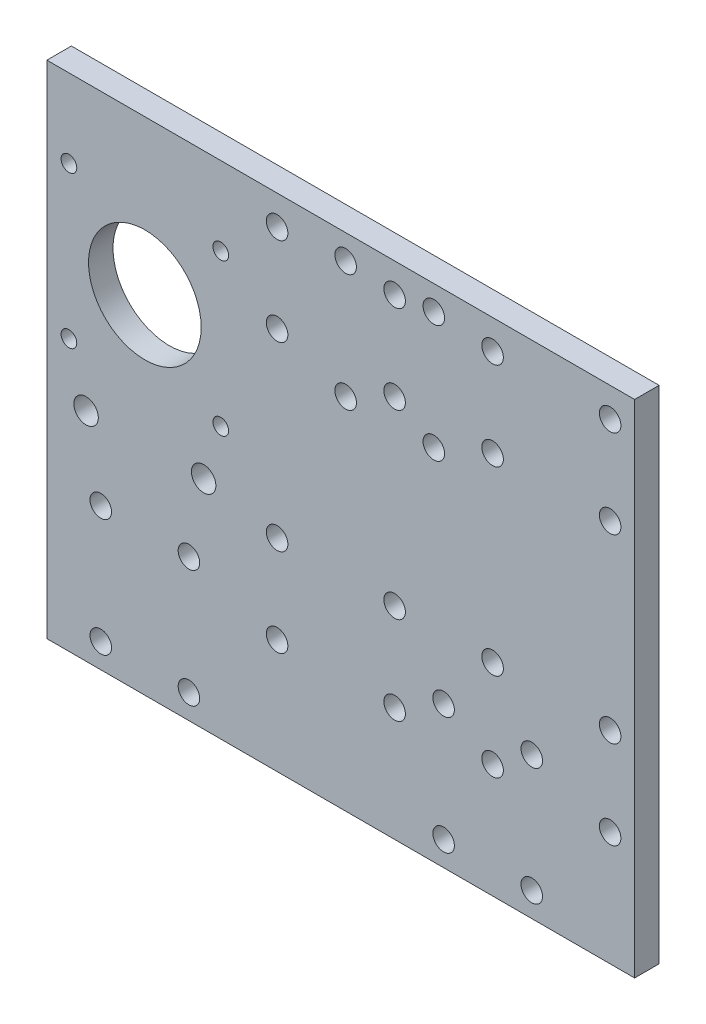
SolidWorks part; units mm, degrees
ref_plane "Front Plane" through (0, 0, 0) normal (0, 0, 1) x (1, 0, 0)
ref_plane "Top Plane" through (0, 0, 0) normal (0, 1, 0) x (1, 0, 0)
ref_plane "Right Plane" through (0, 0, 0) normal (1, 0, 0) x (0, 0, -1)
sketch "Sketch1" plane through (0, 0, 0) normal (0, 0, 1) x (1, 0, 0)
  line L1 (-60, 51.15) -> (60, 51.15)
  line L2 (-60, 51.15) -> (-60, -51.15)
  line L3 (-60, -51.15) -> (60, -51.15)
  line L4 (60, 51.15) -> (60, -51.15)
  line L5 (-60, 51.15) -> (60, -51.15) construction
  line L6 (-60, -51.15) -> (60, 51.15) construction
  point P0 (0, 0)
  dimension "D1" = 102.3
  dimension "D2" = 120
extrude "Boss-Extrude1" add sketch "Sketch1" along normal blind 5
sketch "Sketch4" plane through (0, 0, 5) normal (0, 0, 1) x (1, 0, 0)
  line L0 (21, -22.15) -> (39, -22.15) construction
  line L1 (39, -22.15) -> (39, -46.15) construction
  line L2 (39, -46.15) -> (21, -46.15) construction
  line L3 (21, -46.15) -> (21, -22.15) construction
  circle A0 centre (39, -22.15) radius 2.2
  circle A1 centre (39, -46.15) radius 2.2
  circle A2 centre (21, -46.15) radius 2.2
  circle A3 centre (21, -22.15) radius 2.2
  dimension "D7" = 4.4
  dimension "D1" = 24
  dimension "D2" = 18
extrude "Cut-Extrude1" cut sketch "Sketch4" against normal blind 5
pattern_linear "LPattern1" count 2 spacing 70 along (-1, 0, 0) of "Cut-Extrude1"
sketch "Sketch6" plane through (0, 0, 5) normal (0, 0, 1) x (1, 0, 0)
  line L0 (-55.5, 35.1494) -> (-24.5, 35.1506) construction
  line L5 (-24.5, 35.1506) -> (-24.5, 4.1506) construction
  line L6 (60, 51.15) -> (-60, 51.15) construction
  line L11 (-55.5, 35.1494) -> (-24.5, 4.1506) construction
  line L12 (-55.5, 4.1494) -> (-24.5, 35.1506) construction
  line L13 (-60, 51.15) -> (-60, -51.15) construction
  line L14 (-24.5, 4.1506) -> (-55.5, 4.1494) construction
  line L15 (-55.5, 4.1494) -> (-55.5, 35.1494) construction
  circle A0 centre (-55.5, 35.1494) radius 1.6
  circle A1 centre (-24.5, 35.1506) radius 1.6
  circle A2 centre (-55.5, 4.1494) radius 1.6
  circle A3 centre (-24.5, 4.1506) radius 1.6
  circle A4 centre (-40, 19.65) radius 11.5
  point P9 (-40, 19.65)
  dimension "D1" = 31.5
  dimension "D2" = 20
  dimension "D3" = 31
  dimension "D4" = 31
extrude "Cut-Extrude4" cut sketch "Sketch6" against normal blind 10
sketch "Sketch8" plane through (0, 0, 5) normal (0, 0, 1) x (1, 0, 0)
  line L0 (11, 27.15) -> (-13, 45.15) construction
  line L5 (-13, 27.15) -> (11, 45.15) construction
  line L6 (60, 51.15) -> (-60, 51.15) construction
  line L11 (1, 22.15) -> (19, 46.15) construction
  line L12 (1, 46.15) -> (19, 22.15) construction
  line L13 (1, 46.15) -> (19, 46.15) construction
  line L14 (19, 46.15) -> (19, 22.15) construction
  line L15 (19, 22.15) -> (1, 22.15) construction
  line L16 (1, 22.15) -> (1, 46.15) construction
  line L17 (60, -51.15) -> (60, 51.15) construction
  line L18 (-13, 27.15) -> (-13, 45.15) construction
  line L19 (-13, 45.15) -> (11, 45.15) construction
  line L20 (11, 45.15) -> (11, 27.15) construction
  line L21 (11, 27.15) -> (-13, 27.15) construction
  line L22 (55, 27.15) -> (31, 45.15) construction
  line L23 (31, 27.15) -> (55, 45.15) construction
  line L24 (31, 27.15) -> (31, 45.15) construction
  line L25 (31, 45.15) -> (55, 45.15) construction
  line L26 (55, 45.15) -> (55, 27.15) construction
  line L27 (55, 27.15) -> (31, 27.15) construction
  line L28 (55, -27.85) -> (31, -9.85) construction
  line L29 (31, -27.85) -> (55, -9.85) construction
  line L30 (31, -27.85) -> (31, -9.85) construction
  line L31 (31, -9.85) -> (55, -9.85) construction
  line L32 (55, -9.85) -> (55, -27.85) construction
  line L33 (55, -27.85) -> (31, -27.85) construction
  line L34 (11, -27.85) -> (-13, -9.85) construction
  line L35 (-13, -27.85) -> (11, -9.85) construction
  line L36 (-13, -27.85) -> (-13, -9.85) construction
  line L37 (-13, -9.85) -> (11, -9.85) construction
  line L38 (11, -9.85) -> (11, -27.85) construction
  line L39 (11, -27.85) -> (-13, -27.85) construction
  line L40 (-1, 36.15) -> (-1, -18.85) construction
  line L41 (-1, -18.85) -> (43, -18.85) construction
  line L42 (43, -18.85) -> (43, 36.15) construction
  line L43 (43, 36.15) -> (-1, 36.15) construction
  circle A0 centre (1, 46.15) radius 2.2
  circle A1 centre (19, 46.15) radius 2.2
  circle A2 centre (1, 22.15) radius 2.2
  circle A3 centre (19, 22.15) radius 2.2
  circle A4 centre (-13, 27.15) radius 2.2
  circle A5 centre (-13, 45.15) radius 2.2
  circle A6 centre (11, 27.15) radius 2.2
  circle A7 centre (11, 45.15) radius 2.2
  circle A8 centre (31, 27.15) radius 2.2
  circle A9 centre (31, 45.15) radius 2.2
  circle A10 centre (55, 27.15) radius 2.2
  circle A11 centre (55, 45.15) radius 2.2
  circle A12 centre (31, -27.85) radius 2.2
  circle A13 centre (31, -9.85) radius 2.2
  circle A14 centre (55, -27.85) radius 2.2
  circle A15 centre (55, -9.85) radius 2.2
  circle A16 centre (-13, -27.85) radius 2.2
  circle A17 centre (-13, -9.85) radius 2.2
  circle A18 centre (11, -27.85) radius 2.2
  circle A19 centre (11, -9.85) radius 2.2
  point P2 (-1, 36.15)
  point P8 (10, 34.15)
  point P22 (43, 36.15)
  point P31 (43, -18.85)
  point P40 (-1, -18.85)
  point P51 (79.3794, 40.2795)
  dimension "D5" = 24
  dimension "D1" = 17
  dimension "D2" = 50
  dimension "D3" = 24
  dimension "D4" = 18
  dimension "D6" = 18
  dimension "D7" = 24
  dimension "D8" = 18
  dimension "D9" = 24
  dimension "D10" = 18
  dimension "D11" = 24
  dimension "D12" = 18
  dimension "D13" = 44
  dimension "D14" = 55
  dimension "D15" = 6
  dimension "D16" = 5
extrude "Cut-Extrude5" cut sketch "Sketch8" against normal blind 10
sketch "Sketch9" plane through (0, 0, 5) normal (0, 0, 1) x (1, 0, 0)
  line L0 (-40, 19.65) -> (-40, -51.15) construction
  line L1 (-60, -51.15) -> (60, -51.15) construction
  line L2 (-52, -6.85) -> (-40, -6.85) construction
  line L3 (-28, -6.85) -> (-40, -6.85) construction
  line L4 (60, 51.15) -> (-60, 51.15) construction
  circle A0 centre (-52, -6.85) radius 2.5
  circle A1 centre (-28, -6.85) radius 2.5
  dimension "D1" = 12
  dimension "D4" = 58
extrude "Cut-Extrude6" cut sketch "Sketch9" against normal blind 10
